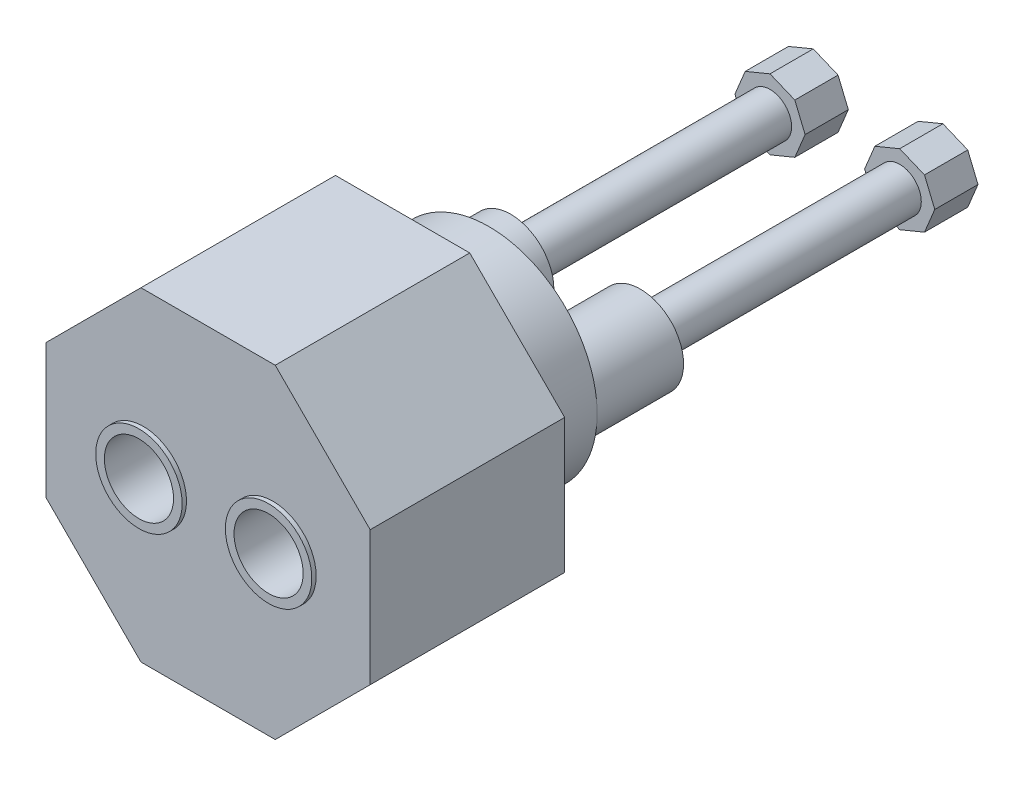
SolidWorks part; units mm, degrees
ref_plane "Front Plane" through (0, 0, 0) normal (0, 0, 1) x (1, 0, 0)
ref_plane "Top Plane" through (0, 0, 0) normal (0, 1, 0) x (1, 0, 0)
ref_plane "Right Plane" through (0, 0, 0) normal (1, 0, 0) x (0, 0, -1)
sketch "Sketch1" plane through (0, 0, 0) normal (0, 0, 1) x (1, 0, 0)
  line L0 (0, 0) -> (15, 0)
  line L1 (15.533, 37.5) -> (-15.533, 37.5)
  line L2 (-15.533, 37.5) -> (-37.5, 15.533)
  line L3 (-37.5, 15.533) -> (-37.5, -15.533)
  line L4 (-37.5, -15.533) -> (-15.533, -37.5)
  line L5 (-15.533, -37.5) -> (15.533, -37.5)
  line L6 (15.533, -37.5) -> (37.5, -15.533)
  line L7 (37.5, -15.533) -> (37.5, 15.533)
  line L8 (37.5, 15.533) -> (15.533, 37.5)
  line L9 (0, 0) -> (-15, 0)
  circle A0 centre (0, 0) radius 37.5 construction
  circle A1 centre (15, 0) radius 10
  circle A2 centre (-15, 0) radius 10
  circle A3 centre (0, 0) radius 25
  dimension "D2" = 15
  dimension "D4" = 20
  dimension "D5" = 20
  dimension "D1" = 75
  dimension "D3" = 15
extrude "Boss-Extrude1" add sketch "Sketch1" along normal blind 45 contours L1 L2 L3 L4 L5 L6 L7 L8
extrude "Boss-Extrude2" add sketch "Sketch1<3>" against normal blind 40 and the other way blind 46 contours A2
sketch "Sketch1<3>" plane through (0, 0, 0) normal (0, 0, 1) x (1, 0, 0) same geometry as "Sketch1"
extrude "Boss-Extrude3" add sketch "Sketch1<4>" against normal blind 40 contours A1
sketch "Sketch1<4>" plane through (0, 0, 0) normal (0, 0, 1) x (1, 0, 0) same geometry as "Sketch1"
extrude "Boss-Extrude4" add sketch "Sketch1<5>" against normal blind 20 contours A3
sketch "Sketch1<5>" plane through (0, 0, 0) normal (0, 0, 1) x (1, 0, 0) same geometry as "Sketch1"
sketch "Sketch2" plane through (0, 0, -40) normal (0, 0, -1) x (-1, 0, 0)
  circle A0 centre (15, 0) radius 5
  dimension "D2" = 10
  dimension "D1" = 15
extrude "Boss-Extrude5" add sketch "Sketch2" along normal blind 60 contours A0
mirror "Mirror2" about plane through (0, 0, 0) normal (1, 0, 0) of "Boss-Extrude5"
sketch "Sketch3" plane through (0, 0, -100) normal (0, 0, -1) x (-1, 0, 0)
  line L1 (-6.8821, 0) -> (-9.2597, 5.7403)
  line L2 (-9.2597, 5.7403) -> (-15, 8.1179)
  line L3 (-15, 8.1179) -> (-20.7403, 5.7403)
  line L4 (-20.7403, 5.7403) -> (-23.1179, 0)
  line L5 (-23.1179, 0) -> (-20.7403, -5.7403)
  line L6 (-20.7403, -5.7403) -> (-15, -8.1179)
  line L7 (-15, -8.1179) -> (-9.2597, -5.7403)
  line L8 (-9.2597, -5.7403) -> (-6.8821, 0)
  circle A0 centre (-15, 0) radius 7.5 construction
extrude "Boss-Extrude6" add sketch "Sketch3" along normal blind 10
mirror "Mirror3" about plane through (0, 0, 0) normal (1, 0, 0) of "Boss-Extrude6"
mirror "Mirror4" about plane through (0, 0, 0) normal (1, 0, 0) of "Boss-Extrude2"
sketch "Sketch4" plane through (0, 0, 46) normal (0, 0, 1) x (1, 0, 0)
  circle A0 centre (-15, 0) radius 8
extrude "Cut-Extrude2" cut sketch "Sketch4" against normal blind 15
mirror "Mirror5" about plane through (0, 0, 0) normal (1, 0, 0) of "Cut-Extrude2"
